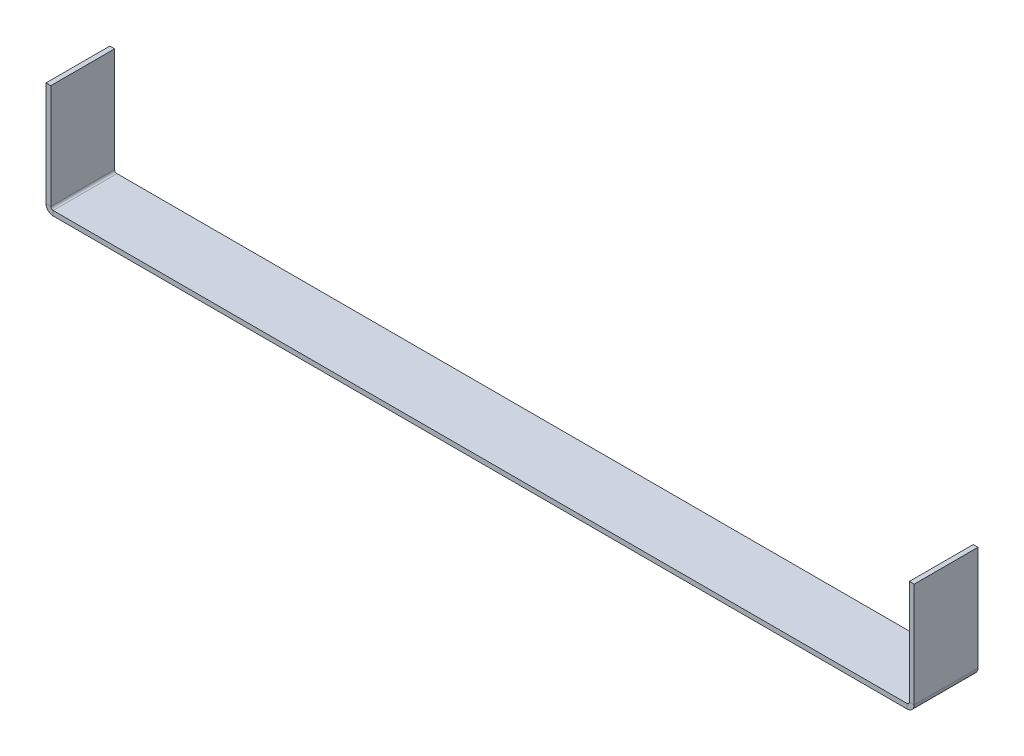
SolidWorks part; units mm, degrees
note: The reader was unsure of these and kept them because the rebuilt part matched: flange length of "Ребро-кромка1", "Ребро-кромка2".
ref_plane "Спереди" through (0, 0, 0) normal (0, 0, 1) x (1, 0, 0)
ref_plane "Сверху" through (0, 0, 0) normal (0, 1, 0) x (1, 0, 0)
ref_plane "Справа" through (0, 0, 0) normal (1, 0, 0) x (0, 0, -1)
sketch "Эскиз1" plane through (0, 0, 0) normal (0, 1, 0) x (1, 0, 0)
  line L1 (0, 0) -> (272, 0)
  line L2 (0, 0) -> (0, 20)
  line L3 (0, 20) -> (272, 20)
  line L4 (272, 0) -> (272, 20)
base flange "Базовая кромка1" sketch "Эскиз1" thickness 1.5 reverse thickness direction no parameters "D1"=0.7366
edge flange "Ребро-кромка1" sketch "Эскиз8" flange angle 90 flange length 35 flange position material inside bend radius 0.7366 thickness 1.5 relief rectangular parameters "D6"=10
sketch "Эскиз8" plane through (0, 0, 0) normal (-1, 0, 0) x (0, 0, 1)
  line L0 (-20, 0) -> (0, 0) construction
  line L1 (-20, 0) -> (0, 0)
  line L2 (-20, 0) -> (-20, 33.5)
  line L3 (-20, 33.5) -> (0, 33.5)
  line L4 (0, 33.5) -> (0, 0)
bend "EdgeBend1" bend radius 0.7366 bend angle 90 parameters "D5"=1
edge flange "Ребро-кромка2" sketch "Эскиз11" flange angle 90 flange length 35 flange position material inside bend radius 0.7366 thickness 1.5 relief rectangular parameters "D6"=10
sketch "Эскиз11" plane through (272, 0, 0) normal (1, 0, 0) x (0, 0, -1)
  line L2 (0, 0) -> (0, 33.5)
  line L3 (0, 33.5) -> (20, 33.5)
  line L4 (20, 33.5) -> (20, 0)
  line L7 (0, 0) -> (20, 0) construction
  line L8 (0, 0) -> (20, 0)
bend "EdgeBend2" bend radius 0.7366 bend angle 90 parameters "D5"=2
sketch "Сгиб-Линии1" [suppressed] plane through (0, 0, 0) normal (0, 1, 0) x (1, 0, 0)
sketch "Граничная рамка1" [suppressed] plane through (0, 0, 0) normal (0, 1, 0) x (1, 0, 0)
sheet metal parameters "Листовой металл1" thickness 1.5 parameters "D1"=0.7366
flat pattern "Развертка1" [suppressed]
sketch "Сгиб-Линии2" plane through (0, 0, 0) normal (0, 1, 0) x (1, 0, 0)
sketch3d "Граничная рамка2" [suppressed]
  line L0 (-200, 20, 0) -> (0, 20, 0) construction
  line L1 (-200, 0, 0) -> (0, 0, 0) construction
  line L2 (-200, 20, 0) -> (-200, 0, 0) construction
  line L3 (0, 20, 0) -> (0, 0, 0) construction
sheet metal parameters "Листовой металл2" thickness 1.5 parameters "D1"=0.7366
flat pattern "Развертка1"
sketch "Сгиб-Линии2" plane through (0, 0, 0) normal (0, 1, 0) x (1, 0, 0)
  line L0 (1.069, 20) -> (1.069, 0) construction
  line L1 (1.069, 20) -> (1.069, 0) construction
sketch3d "Граничная рамка2" [suppressed]
  line L0 (200, 20, 0) -> (-30.5985, 20, 0) construction
  line L1 (200, 0, 0) -> (-30.5985, 0, 0) construction
  line L2 (200, 20, 0) -> (200, 0, 0) construction
  line L3 (-30.5985, 20, 0) -> (-30.5985, 0, 0) construction
bend of the flat pattern "Плоское состояние-<EdgeBend1>1"
sheet metal parameters "Листовой металл3" thickness 1.5 parameters "D1"=0.7366
flat pattern "Развертка1"
sketch "Сгиб-Линии2" plane through (0, 0, 0) normal (0, 1, 0) x (1, 0, 0)
  line L0 (1.069, 20) -> (1.069, 0) construction
  line L1 (1.069, 20) -> (1.069, 0) construction
  line L2 (270.931, 0) -> (270.931, 20) construction
  line L3 (270.931, 0) -> (270.931, 20) construction
sketch3d "Граничная рамка2" [suppressed]
  line L0 (304.8619, 20, 0) -> (-32.8619, 20, 0) construction
  line L1 (304.8619, 0, 0) -> (-32.8619, 0, 0) construction
  line L2 (304.8619, 20, 0) -> (304.8619, 0, 0) construction
  line L3 (-32.8619, 20, 0) -> (-32.8619, 0, 0) construction
bend of the flat pattern "Плоское состояние-<EdgeBend1>1"
bend of the flat pattern "Плоское состояние-<EdgeBend2>1"
